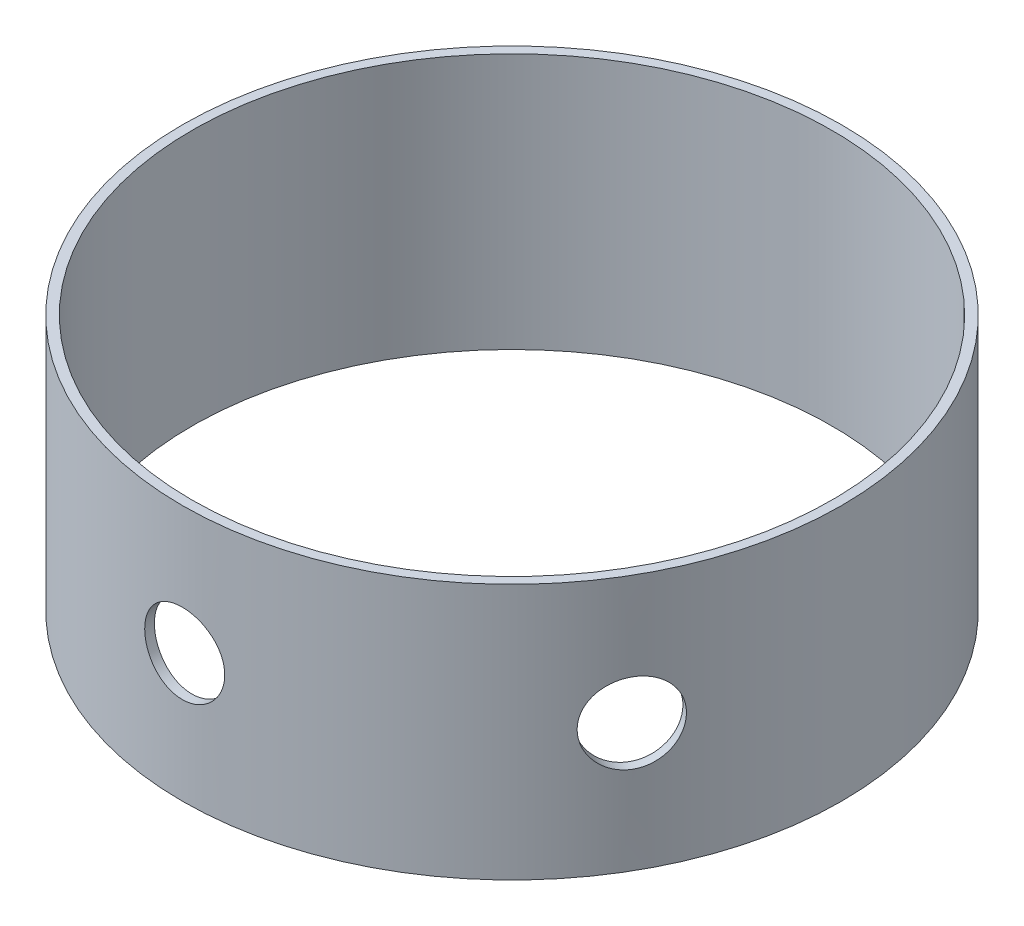
SolidWorks part; units mm, degrees
ref_plane "Front Plane" through (0, 0, 0) normal (0, 0, 1) x (1, 0, 0)
ref_plane "Top Plane" through (0, 0, 0) normal (0, 1, 0) x (1, 0, 0)
ref_plane "Right Plane" through (0, 0, 0) normal (1, 0, 0) x (0, 0, -1)
sketch "Sketch1" plane through (0, 0, 0) normal (0, 1, 0) x (1, 0, 0)
  circle A0 centre (0, 0) radius 65.405
  circle A1 centre (0, 0) radius 63.5
  dimension "D1" = 130.81
  dimension "D2" = 127
extrude "Boss-Extrude1" add sketch "Sketch1" along normal mid plane 50.8
ref_plane "Plane1" through (0, 0, 65.405) normal (0, 0, 1) x (1, 0, 0)
ref_plane "Plane2" through (56.6424, 0, 32.7025) normal (0.866, 0, 0.5) x (0, -1, 0)
hole_wizard "5/8 (0.625) Diameter Hole1" positions "Sketch2" profile "Sketch3" hole size "5/8" standard "ANSI Inch"
sketch "Sketch2" plane through (56.6424, 0, 32.7025) normal (0.866, 0, 0.5) x (0, -1, 0)
  point P0 (0, 0)
  point P3 (0, 0)
sketch "Sketch3" plane through (56.6424, 0, 32.7025) normal (0, 1, 0) x (0.5, 0, -0.866)
  line L0 (0, 0) -> (0, 3.81)
  line L1 (0, 3.81) -> (7.9375, 3.81)
  line L2 (7.9375, 3.81) -> (7.9375, 0)
  line L5 (7.9375, 0) -> (0, 0)
  line L10 (0, 3.81) -> (-7.9375, 3.81) construction
  line L11 (0, -6.35) -> (0, 107.95) construction
  dimension "Hole Dia." = 15.875
  dimension "Hole Depth" = 3.81
  dimension "Drill Angle" = 180
hole_wizard "5/8 (0.625) Diameter Hole2" positions "Sketch4" profile "Sketch5" hole size "5/8" standard "ANSI Inch"
sketch "Sketch4" plane through (0, 0, 65.405) normal (0, 0, 1) x (1, 0, 0)
  point P0 (0, 0)
sketch "Sketch5" plane through (0, 0, 65.405) normal (1, 0, 0) x (0, -1, 0)
  line L0 (0, 0) -> (0, 3.81)
  line L1 (0, 3.81) -> (7.9375, 3.81)
  line L2 (7.9375, 3.81) -> (7.9375, 0)
  line L5 (7.9375, 0) -> (0, 0)
  line L10 (0, 3.81) -> (-7.9375, 3.81) construction
  line L11 (0, -6.35) -> (0, 107.95) construction
  dimension "Hole Dia." = 15.875
  dimension "Hole Depth" = 3.81
  dimension "Drill Angle" = 180
